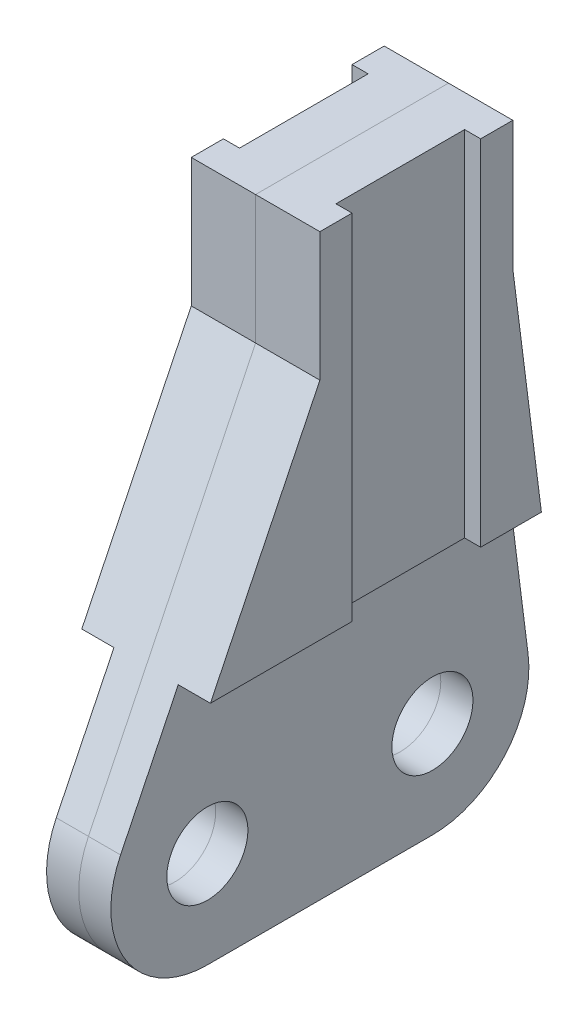
SolidWorks part; units mm, degrees
ref_plane "Front Plane" through (0, 0, 0) normal (0, 0, 1) x (1, 0, 0)
ref_plane "Top Plane" through (0, 0, 0) normal (0, 1, 0) x (1, 0, 0)
ref_plane "Right Plane" through (0, 0, 0) normal (1, 0, 0) x (0, 0, -1)
sketch "Sketch1" plane through (0, 0, 0) normal (1, 0, 0) x (0, 0, -1)
  line L0 (-22.225, -41.275) -> (22.225, -41.275) construction
  line L1 (0, -41.275) -> (0, 60.325) construction
  line L2 (-6.35, 34.925) -> (31.75, 34.925) construction
  line L3 (-22.225, -60.325) -> (22.225, -60.325)
  line L4 (0, 60.325) -> (31.75, 60.325)
  line L5 (-6.35, 60.325) -> (-6.35, 34.925)
  line L6 (0, 60.325) -> (-6.35, 60.325)
  line L7 (31.75, 60.325) -> (31.75, 34.925)
  line L8 (-6.35, 34.925) -> (-39.3565, -32.9434)
  line L9 (31.75, 34.925) -> (41.1232, -38.8748)
  circle A0 centre (-22.225, -41.275) radius 8.001
  circle A1 centre (22.225, -41.275) radius 8.001
  circle A2 centre (-22.225, -41.275) radius 19.05
  circle A3 centre (22.225, -41.275) radius 19.05
extrude "Boss-Extrude1" add sketch "Sketch1" along normal blind 12.7 contours A3 L9 L7 L4 L6 L5 L8 A2 L3 | A3 A1 | A2 A0 region at (0, 6.6516, -7.5075) region at (0, -51.0933, 37.9178) region at (0, -29.038, -8.3355)
sketch "Sketch2" plane through (12.7, 0, 0) normal (1, 0, 0) x (0, 0, -1)
  line L0 (-22.225, -60.325) -> (22.225, -60.325) construction
  line L1 (-22.225, -60.325) -> (22.225, -60.325)
  line L2 (-22.225, -41.275) -> (22.225, -41.275) construction
  line L3 (-22.225, -22.225) -> (22.225, -22.225)
  line L4 (-22.225, -60.325) -> (22.225, -60.325)
  line L5 (0, 60.325) -> (0, -22.225)
  line L6 (-6.35, 60.325) -> (31.75, 60.325) construction
  line L7 (25.4, -22.4914) -> (25.4, 60.325)
  line L8 (31.75, 60.325) -> (31.75, 34.925) construction
  line L11 (-63.9631, -73.025) -> (63.9631, -73.025)
  line L12 (-63.9631, -73.025) -> (-63.9631, -9.525)
  line L13 (-63.9631, -9.525) -> (63.9631, -9.525)
  line L14 (63.9631, -73.025) -> (63.9631, -9.525)
  line L15 (-63.9631, -73.025) -> (63.9631, -9.525) construction
  line L16 (-63.9631, -9.525) -> (63.9631, -73.025) construction
  circle A0 centre (22.225, -41.275) radius 8.001 construction
  circle A1 centre (-22.225, -41.275) radius 8.001 construction
  circle A2 centre (22.225, -41.275) radius 8.001
  circle A3 centre (-22.225, -41.275) radius 8.001
  arc A4 (-22.225, -22.225) -> (-22.225, -60.325) centre (-22.225, -41.275) ccw
  arc A5 (22.225, -60.325) -> (22.225, -22.225) centre (22.225, -41.275) ccw
  point P8 (0, -41.275)
  point P23 (0, -41.275)
  line M12 (31.75, 60.325) -> (-6.35, 60.325)
  dimension "D1" = 6.35
  dimension "D2" = 63.5
extrude "Cut-Extrude1" cut sketch "Sketch2" against normal blind 6.35 contours L13 L14 L11 L12
extrude "Cut-Extrude2" cut sketch "Sketch2<3>" against normal blind 3.175 contours L3 L13 L7 L5 M12 region at (12.7, 25.4, -12.7)
sketch "Sketch2<3>" plane through (12.7, 0, 0) normal (1, 0, 0) x (0, 0, -1) same geometry as "Sketch2"
mirror "Mirror1" about plane through (0, 0, 0) normal (1, 0, 0) of bodies 103
sketch "Sketch3" plane through (0, 0, 0) normal (1, 0, 0) x (0, 0, -1)
  line L0 (12.7, 60.325) -> (12.7, -60.325) construction
  line L1 (-6.35, 60.325) -> (31.75, 60.325) construction
  line L2 (-22.225, -60.325) -> (22.225, -60.325) construction
  circle A0 centre (12.7, 9.525) radius 6.5484
  circle A1 centre (12.7, 47.625) radius 6.5484
  dimension "D3" = 13.0969
  dimension "D1" = 50.8
  dimension "D2" = 12.7
extrude "Cut-Extrude3" cut sketch "Sketch3" against normal through all
